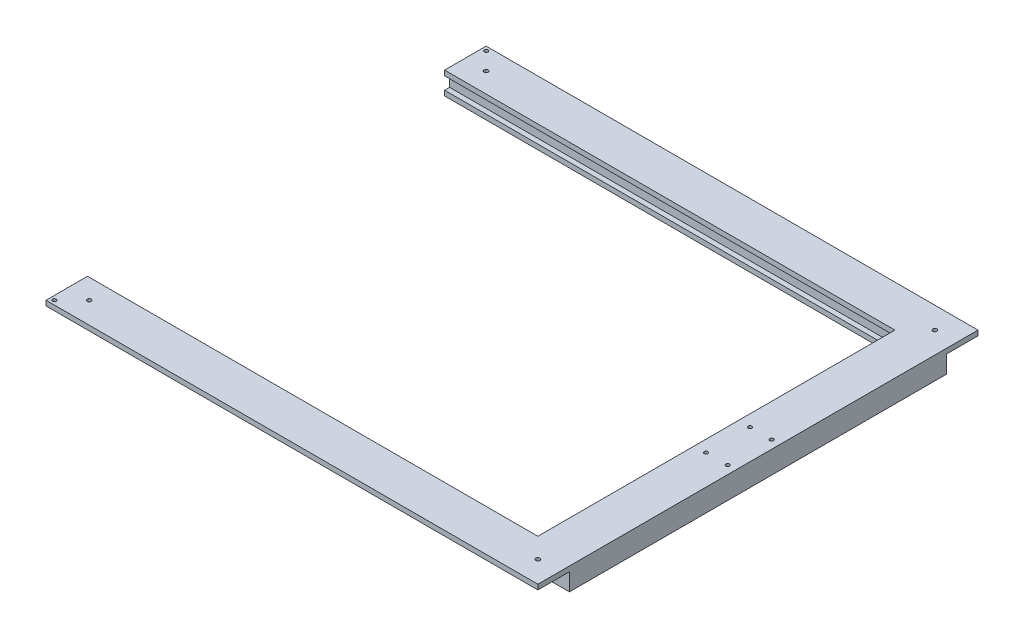
SolidWorks part; units mm, degrees
ref_plane "Спереди" through (0, 0, 0) normal (0, 0, 1) x (1, 0, 0)
ref_plane "Сверху" through (0, 0, 0) normal (0, 1, 0) x (1, 0, 0)
ref_plane "Справа" through (0, 0, 0) normal (1, 0, 0) x (0, 0, -1)
sketch "Эскиз1" plane through (0, 0, 0) normal (0, 1, 0) x (1, 0, 0)
  line L0 (50, -77.9215) -> (50, -607.9215)
  line L1 (-542.3, -77.9215) -> (50, -77.9215)
  line L2 (-542.3, -77.9215) -> (-542.3, -127.9215)
  line L3 (-542.3, -607.9215) -> (50, -607.9215)
  line L5 (-542.3, -127.9215) -> (0, -127.9215)
  line L7 (-542.3, -557.9215) -> (0, -557.9215)
  line L13 (-542.3, -557.9215) -> (-542.3, -607.9215)
  line L22 (0, -127.9215) -> (0, -557.9215)
  dimension "D1" = 592.3
  dimension "D12" = 50
  dimension "D2" = 530
  dimension "D3" = 50
  dimension "D4" = 50
  dimension "D9" = 50
  dimension "D8" = 77.9215
extrude "Бобышка-Вытянуть2" add sketch "Эскиз1" along normal blind 6
sketch "Эскиз2" plane through (0, 0, 0) normal (0, -1, 0) x (1, 0, 0)
  line L0 (-542.3, 127.9215) -> (0, 127.9215) construction
  line L5 (50, 607.9215) -> (50, 77.9215) construction
  line L6 (0, 557.9215) -> (-542.3, 557.9215) construction
  line L18 (50, 569.9215) -> (50, 115.9215)
  line L20 (6, 563.9215) -> (6, 121.9215)
  line L21 (-542.3, 77.9215) -> (-542.3, 127.9215) construction
  line L22 (50, 115.9215) -> (-542.3, 115.9215)
  line L24 (6, 121.9215) -> (-542.3, 121.9215)
  line L25 (-542.3, 115.9215) -> (-542.3, 121.9215)
  line L26 (-542.3, 557.9215) -> (-542.3, 607.9215) construction
  line L27 (50, 569.9215) -> (-542.3, 569.9215)
  line L29 (6, 563.9215) -> (-542.3, 563.9215)
  line L30 (-542.3, 569.9215) -> (-542.3, 563.9215)
  dimension "D1" = 44
  dimension "D2" = 6
  dimension "D3" = 6
  dimension "D4" = 6
  dimension "D5" = 6
extrude "Бобышка-Вытянуть3" add sketch "Эскиз2" along normal blind 15
sketch "Эскиз4" plane through (0, 6, 0) normal (0, 1, 0) x (1, 0, 0)
  line L0 (50, -77.9215) -> (-542.3, -77.9215) construction
  line L1 (-542.3, -77.9215) -> (-542.3, -127.9215) construction
  circle A0 centre (-516.3, -103.9215) radius 2.5
  dimension "D1" = 5
  dimension "D2" = 26
  dimension "D3" = 26
extrude "Вырез-Вытянуть1" cut sketch "Эскиз4" against normal through all
pattern_linear "Линейный массив2" count 2 spacing 540.3 along (1, 0, 0) count 2 spacing 478 along (0, 0, 1) of "Вырез-Вытянуть1"
sketch "Эскиз5" plane through (0, -15, 0) normal (0, -1, 0) x (1, 0, 0)
  line L8 (50, 569.9215) -> (-542.3, 569.9215)
  line L9 (-542.3, 569.9215) -> (-542.3, 557.9215)
  line L10 (-542.3, 557.9215) -> (0, 557.9215)
  line L11 (0, 557.9215) -> (0, 127.9215)
  line L12 (0, 127.9215) -> (-542.3, 127.9215)
  line L13 (-542.3, 127.9215) -> (-542.3, 115.9215)
  line L14 (-542.3, 115.9215) -> (50, 115.9215)
  line L15 (50, 115.9215) -> (50, 569.9215)
extrude "Бобышка-Вытянуть4" add sketch "Эскиз5" along normal blind 6
sketch "Эскиз6" plane through (0, -21, 0) normal (0, -1, 0) x (1, 0, 0)
  line L0 (40, 342.9215) -> (50, 342.9215) construction
  line L1 (40, 316.4215) -> (14, 316.4215) construction
  line L2 (40, 316.4215) -> (40, 369.4215) construction
  line L3 (40, 369.4215) -> (14, 369.4215) construction
  line L4 (14, 316.4215) -> (14, 369.4215) construction
  line L5 (50, 115.9215) -> (50, 569.9215) construction
  circle A1 centre (14, 369.4215) radius 2.25
  circle A2 centre (40, 369.4215) radius 2.25
  circle A3 centre (40, 316.4215) radius 2.25
  circle A4 centre (14, 316.4215) radius 2.25
  point P4 (50, 342.9215)
  point P6 (40, 342.9215)
  dimension "D4" = 4.5
  dimension "D1" = 53
  dimension "D2" = 26
  dimension "D3" = 10
extrude "Вырез-Вытянуть2" cut sketch "Эскиз6" against normal through all
sketch "Эскиз7" plane through (0, 0, 0) normal (0, -1, 0) x (1, 0, 0)
  line L0 (-542.3, 597.9215) -> (-532.3, 607.9215) construction
  line L1 (-542.3, 607.9215) -> (-532.3, 607.9215) construction
  line L2 (-542.3, 607.9215) -> (-542.3, 597.9215) construction
  line L3 (-542.3, 597.9215) -> (-532.3, 597.9215) construction
  line L4 (-532.3, 607.9215) -> (-532.3, 597.9215) construction
  line L5 (-542.3, 607.9215) -> (-532.3, 597.9215) construction
  line L6 (-532.3, 87.9215) -> (-542.3, 77.9215) construction
  line L7 (-542.3, 77.9215) -> (-532.3, 77.9215) construction
  line L8 (-542.3, 77.9215) -> (-542.3, 87.9215) construction
  line L9 (-542.3, 87.9215) -> (-532.3, 87.9215) construction
  line L10 (-532.3, 77.9215) -> (-532.3, 87.9215) construction
  line L11 (-542.3, 87.9215) -> (-532.3, 77.9215) construction
  circle A0 centre (-537.3, 602.9215) radius 2.25
  circle A1 centre (-537.3, 82.9215) radius 2.25
  point P12 (-537.3, 82.9215)
  dimension "D3" = 4.5
  dimension "D6" = 4.5
  dimension "D1" = 10
  dimension "D2" = 10
  dimension "D4" = 10
  dimension "D5" = 10
extrude "Вырез-Вытянуть3" cut sketch "Эскиз7" against normal through all
equation "\"Ширина груза\"= 420"
equation "\"Глубина груза\"= 490"
equation "\"Высота груза\"= 297"
equation "\"Ширина ячейки\"= \"Ширина груза\" + 10"
equation "\"Глубина ячейки\"= \"Глубина груза\" + 10"
equation "\"Высота ячейки\"= \"Высота груза\" + 10 + 13"
equation "\"Колво ячеек ширина\"= 2"
equation "\"Колво ячеек высота\"= 2"
equation "\"Толщина стенки\" = 6"
equation "\"Крепление дверцы\"= 5"
equation "\"Ширина рейки\"= \"Толщина шестерни\""
equation "\"Высота рейки\"= 20"
equation "\"Высота пола\"= 20"
equation "\"Колво полозьев\"= 5"
equation "\"Отступ рейки\"= 20"
equation "\"Глубина каретки\"= \"Глубина ячейки\" + 30 + \"Мотор Y высота корпуса\" + 20"
equation "\"Длинна рейки\"= ( \"Ширина ячейки\" + \"Толщина стенки\" + \"Крепление дверцы\" ) * \"Колво ячеек ширина\" + \"Ширина ячейки выгрузки\" * \"Колво выгрузки\" + \"Толщина стенки\""
equation "\"Отступ шпильки\"= 26"
equation "\"Диаметр шпильки\"= 5"
equation "\"Длинна шпильки\"= ( \"Высота ячейки\" + \"Толщина стенки\" + \"Высота пола\" ) * \"Колво ячеек высота\" + ( \"Толщина стенки\" + \"Отступ рейки\" ) * 2 "
equation "\"D2@Эскиз1\"=\"Ширина ячейки\" + \"Ширина пластины\" * 2 "
equation "\"D9@Эскиз1\"=\"Ширина пластины\""
equation "\"D3@Эскиз1\"=\"Ширина пластины\""
equation "\"D4@Эскиз1\"= \"Ширина пластины\""
equation "\"Ширина пластины\"= 50  "
equation "\"D1@Бобышка-Вытянуть2\"=\"Толщина стенки\""
equation "\"D1@Эскиз4\"= \"Диаметр шпильки\""
equation "\"D4@Линейный массив2\"=\"Ширина ячейки\" + \"Ширина пластины\" * 2  - \"Отступ шпильки\" * 2"
equation "\"D1@Эскиз1\"= \"Глубина каретки\""
equation "\"D3@Линейный массив2\"= \"Глубина каретки\" - \"Отступ шпильки\" * 2"
equation "\"D2@Эскиз4\"=\"Отступ шпильки\""
equation "\"D3@Эскиз4\"= \"Отступ шпильки\""
equation "\"D1@Эскиз2\"= \"Ширина пластины\" - \"Толщина стенки\""
equation "\"D2@Эскиз2\"= \"Толщина стенки\""
equation "\"D3@Эскиз2\"= \"Толщина стенки\""
equation "\"D4@Эскиз2\"= \"Толщина стенки\""
equation "\"D5@Эскиз2\"= \"Толщина стенки\""
equation "\"D1@Бобышка-Вытянуть4\"= \"Толщина стенки\""
equation "\"Вы\"=20"
equation "\"D1@Бобышка-Вытянуть3\"=\"Высота пола\" - 5"
equation "\"Высота зона выгрузки\"= \"Высота ячейки\" * 2 + \"Толщина стенки\" * 2"
equation "\"Колво выгрузки\"= 1"
equation "\"Ширина ячейки выгрузки\"= \"Ширина ячейки\" + \"Толщина стенки\" + \"Отступ крепления мотора фиксации\"*2"
equation "\"Отступ крепления мотора фиксации\" = 30"
equation "\"Мотор X ширина корпуса\"= 42.3"
equation "\"Мотор X высота корпуса\"= 42.3"
equation "\"Мотор X длина корпуса\"= 40"
equation "\"Мотор X вылет вала\"= 19.8"
equation "\"Мотор Y ширина корпуса\"= 42.3"
equation "\"Мотор Y высота корпуса\"= 42.3"
equation "\"Мотор Y длина корпуса\"= 48"
equation "\"Мотор Y вылет вала\"= 30"
equation "\"Мотор Z ширина корпуса\"= 42"
equation "\"Мотор Z высота корпуса\"= 42"
equation "\"Мотор Z длина корпуса\"= 40"
equation "\"Мотор Z вылет вала\"= 23"
equation "\"Мотор диаметр вала ПРЕДВ\"= 5"
equation "\"Мотор шаг крепления ПРЕДВ\"= 31"
equation "\"Мотор диаметр отверстий ПРЕДВ\"= 3"
equation "\"Мотор глубина отверстий ПРЕДВ\"= 4.5"
equation "\"Мотор диаметр буртика ПРЕДВ\"= 22"
equation "\"Мотор высота буртика ПРЕДВ\"= 2"
equation "\"Мотор диаметр шкива ПРЕДВ\"= 16"
equation "\"Мотор длина шкива ПРЕДВ\"= 12"
equation "\"Мотор отступ шкива ПРЕДВ\"= 5"
equation "\"Мотор X шаг градусов\"= 1.8"
equation "\"Мотор X ток А\"= 1.5"
equation "\"Мотор X сопротивление Ом\"= 1.3"
equation "\"Мотор X индуктивность мГн\"= 2"
equation "\"Мотор Y шаг градусов\"= 1.8"
equation "\"Мотор Y ток А\"= 2.2"
equation "\"Мотор Y сопротивление Ом\"= 0.9"
equation "\"Мотор Y индуктивность мГн\"= 2"
equation "\"Мотор Z шаг градусов\"= 1.8"
equation "\"Мотор Z ток А\"= 1"
equation "\"Мотор Z сопротивление Ом\"= 4"
equation "\"Мотор Z индуктивность мГн\"= 8"
equation "\"Мотор Y диаметр ротора\"= 25.78"
